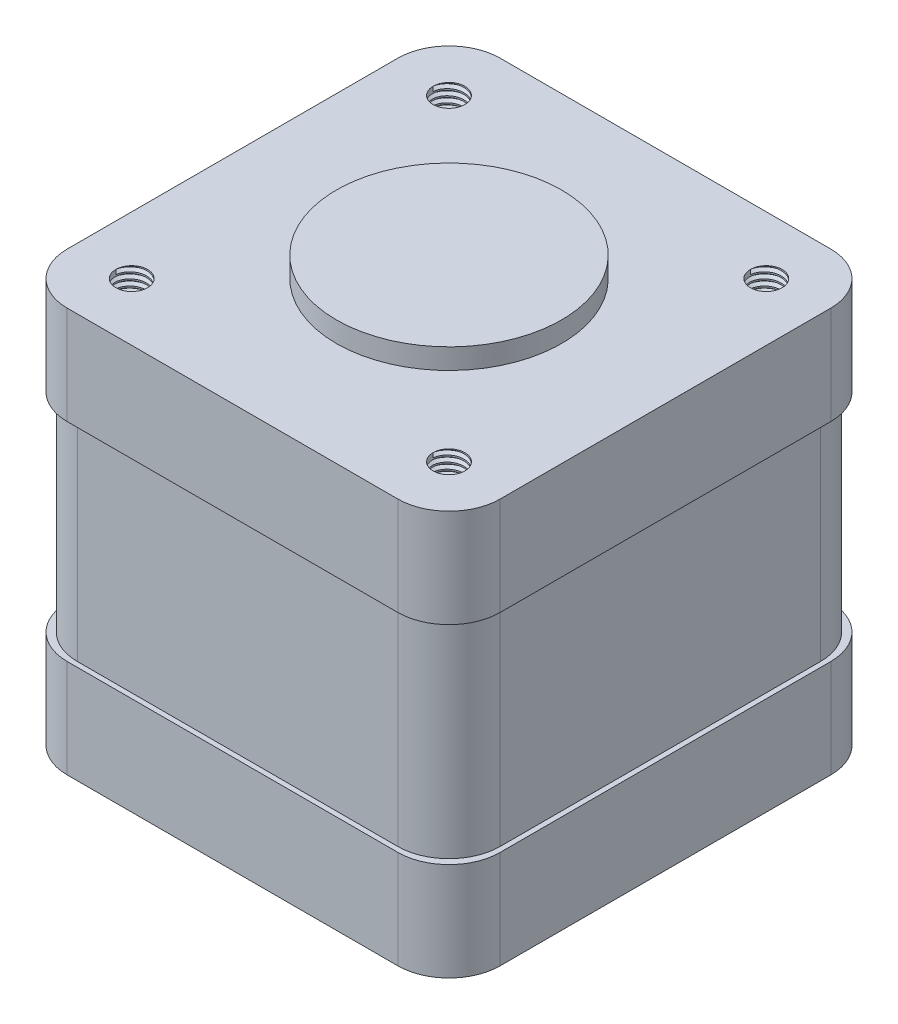
SolidWorks part; units mm, degrees
ref_plane "Front Plane" through (0, 0, 0) normal (0, 0, 1) x (1, 0, 0)
ref_plane "Top Plane" through (0, 0, 0) normal (0, 1, 0) x (1, 0, 0)
ref_plane "Right Plane" through (0, 0, 0) normal (1, 0, 0) x (0, 0, -1)
sketch "Sketch1" plane through (0, 0, 0) normal (0, 1, 0) x (1, 0, 0)
  line L1 (5, 0) -> (37.3, 0)
  line L2 (0, 5) -> (0, 37.3)
  line L3 (5, 42.3) -> (37.3, 42.3)
  line L4 (42.3, 5) -> (42.3, 37.3)
  arc A0 (5, 0) -> (0, 5) centre (5, 5) cw
  arc A1 (37.3, 0) -> (42.3, 5) centre (37.3, 5) ccw
  arc A2 (37.3, 42.3) -> (42.3, 37.3) centre (37.3, 37.3) cw
  arc A3 (0, 37.3) -> (5, 42.3) centre (5, 37.3) cw
  point P7 (0, 0)
  point P12 (42.3, 42.3)
  point P15 (0, 42.3)
  dimension "D3" = 5
  dimension "D1" = 42.3
  dimension "D2" = 42.3
extrude "Boss-Extrude1" add sketch "Sketch1" along normal blind 9.6
sketch "Sketch2" plane through (0, 9.6, 0) normal (0, 1, 0) x (1, 0, 0)
  line L0 (0, 37.3) -> (0, 5) construction
  line L1 (5.5, 0.4967) -> (36.8, 0.4967)
  line L2 (0.5, 5.4967) -> (0.5, 36.8)
  line L3 (5.5, 41.8) -> (36.8, 41.8)
  line L4 (41.8, 5.4967) -> (41.8, 36.8)
  line L5 (37.3, 42.3) -> (5, 42.3) construction
  line L6 (42.3, 5) -> (42.3, 37.3) construction
  line L7 (5, 0) -> (37.3, 0) construction
  arc A0 (5.5, 0.4967) -> (0.5, 5.4967) centre (5.5, 5.4967) cw
  arc A1 (36.8, 0.4967) -> (41.8, 5.4967) centre (36.8, 5.4967) ccw
  arc A2 (36.8, 41.8) -> (41.8, 36.8) centre (36.8, 36.8) cw
  arc A3 (0.5, 36.8) -> (5.5, 41.8) centre (5.5, 36.8) cw
  dimension "D5" = 5
  dimension "D1" = 0.5
  dimension "D2" = 0.5
  dimension "D3" = 0.5
  dimension "D4" = 0.4967
extrude "Boss-Extrude2" add sketch "Sketch2" along normal blind 20.3
sketch "Sketch3" plane through (0, 29.9, 0) normal (0, 1, 0) x (1, 0, 0)
  line L0 (0, 37.3) -> (0, 5) construction
  line L1 (5, 42.3) -> (37.3, 42.3)
  line L2 (0, 37.3) -> (0, 5)
  line L3 (5, 0) -> (37.3, 0)
  line L4 (42.3, 37.3) -> (42.3, 5)
  line L5 (37.3, 42.3) -> (5, 42.3) construction
  line L7 (5.5, 0.4967) -> (36.8, 0.4967) construction
  line L8 (41.8, 5.4967) -> (41.8, 36.8) construction
  arc A0 (37.3, 42.3) -> (42.3, 37.3) centre (37.3, 37.3) cw
  arc A1 (37.3, 0) -> (42.3, 5) centre (37.3, 5) ccw
  arc A2 (0, 5) -> (5, 0) centre (5, 5) ccw
  arc A3 (5, 42.3) -> (0, 37.3) centre (5, 37.3) ccw
  point P10 (42.3, 42.3)
  point P15 (0, 0)
  point P18 (0, 42.3)
  dimension "D3" = 5
  dimension "D4" = 0.4967
  dimension "D1" = 42.3
  dimension "D2" = 42.3
  dimension "D5" = 0.5
extrude "Boss-Extrude3" add sketch "Sketch3" along normal blind 9.6
sketch "Sketch4" plane through (0, 39.5, 0) normal (0, 1, 0) x (1, 0, 0)
  line L0 (21.15, 42.3) -> (21.15, 0) construction
  line L1 (37.3, 42.3) -> (5, 42.3) construction
  line L2 (5, 0) -> (37.3, 0) construction
  line L3 (0, 21.15) -> (42.3, 21.15) construction
  line L4 (0, 37.3) -> (0, 5) construction
  line L5 (42.3, 5) -> (42.3, 37.3) construction
  circle A0 centre (5.65, 36.65) radius 1.55
  circle A1 centre (36.65, 36.65) radius 1.55
  circle A2 centre (5.65, 5.65) radius 1.55
  circle A3 centre (36.65, 5.65) radius 1.55
  point P14 (21.15, 21.15)
  dimension "D2" = 15.5
  dimension "D3" = 3.1
  dimension "D1" = 15.5
extrude "Cut-Extrude1" cut sketch "Sketch4" against normal blind 4.5
thread "MinColWidth_OnTracking2" pitch 0.6 start angle 0, offset 0, length 4.5, pitch 0.6, diameter 3.1
ref_plane "Plane2" through (4.1, 39.5, -36.65) normal (0, 0, 1) x (-1, 0, 0)
sketch "HeaderRowsCount2" plane through (4.1, 39.5, -36.65) normal (0, 0, 1) x (-1, 0, 0)
  line L0 (0, 0) -> (0, 0.6) construction
  line L1 (0, 0) -> (0.3248, 0.1875)
  line L2 (0.3248, 0.1875) -> (0.3248, 0.2625)
  line L3 (0.3248, 0.2625) -> (0, 0.45)
  line L4 (0.3248, 0.225) -> (0, 0.225) construction
  line L11 (0, 0) -> (0, 0.45)
  point P2 (0, 0)
  dimension "Pitch" = 0.6
  dimension "Profile_Angle" = 60
  dimension "Profile_Land" = 0.075
  dimension "Profile_Height" = 0.3248
thread "MinColWidth_OnTracking3" pitch 0.6 profile "HeaderRowsCount3" start angle 0, offset 0, length 4.5, pitch 0.6, diameter 3.1
ref_plane "Plane3" through (35.1, 39.5, -36.65) normal (0, 0, 1) x (-1, 0, 0)
sketch "HeaderRowsCount3" plane through (35.1, 39.5, -36.65) normal (0, 0, 1) x (-1, 0, 0)
  line L0 (0, 0) -> (0, 0.6) construction
  line L1 (0, 0) -> (0.3248, 0.1875)
  line L2 (0.3248, 0.1875) -> (0.3248, 0.2625)
  line L3 (0.3248, 0.2625) -> (0, 0.45)
  line L4 (0.3248, 0.225) -> (0, 0.225) construction
  line L11 (0, 0) -> (0, 0.45)
  point P2 (0, 0)
  dimension "Pitch" = 0.6
  dimension "Profile_Angle" = 60
  dimension "Profile_Land" = 0.075
  dimension "Profile_Height" = 0.3248
thread "MinColWidth_OnTracking4" pitch 0.6 profile "HeaderRowsCount4" start angle 0, offset 0, length 4.5, pitch 0.6, diameter 3.1
ref_plane "Plane4" through (4.1, 39.5, -5.65) normal (0, 0, 1) x (-1, 0, 0)
sketch "HeaderRowsCount4" plane through (4.1, 39.5, -5.65) normal (0, 0, 1) x (-1, 0, 0)
  line L0 (0, 0) -> (0, 0.6) construction
  line L1 (0, 0) -> (0.3248, 0.1875)
  line L2 (0.3248, 0.1875) -> (0.3248, 0.2625)
  line L3 (0.3248, 0.2625) -> (0, 0.45)
  line L4 (0.3248, 0.225) -> (0, 0.225) construction
  line L11 (0, 0) -> (0, 0.45)
  point P2 (0, 0)
  dimension "Pitch" = 0.6
  dimension "Profile_Angle" = 60
  dimension "Profile_Land" = 0.075
  dimension "Profile_Height" = 0.3248
thread "MinColWidth_OnTracking5" pitch 0.6 profile "HeaderRowsCount5" start angle 0, offset 0, length 4.5, pitch 0.6, diameter 3.1
ref_plane "Plane5" through (35.1, 39.5, -5.65) normal (0, 0, 1) x (-1, 0, 0)
sketch "HeaderRowsCount5" plane through (35.1, 39.5, -5.65) normal (0, 0, 1) x (-1, 0, 0)
  line L0 (0, 0) -> (0, 0.6) construction
  line L1 (0, 0) -> (0.3248, 0.1875)
  line L2 (0.3248, 0.1875) -> (0.3248, 0.2625)
  line L3 (0.3248, 0.2625) -> (0, 0.45)
  line L4 (0.3248, 0.225) -> (0, 0.225) construction
  line L11 (0, 0) -> (0, 0.45)
  point P2 (0, 0)
  dimension "Pitch" = 0.6
  dimension "Profile_Angle" = 60
  dimension "Profile_Land" = 0.075
  dimension "Profile_Height" = 0.3248
sketch "Sketch18" plane through (0, 39.5, 0) normal (0, 1, 0) x (1, 0, 0)
  line L0 (0, 21.15) -> (42.3, 21.15) construction
  line L1 (0, 37.3) -> (0, 5) construction
  line L2 (42.3, 5) -> (42.3, 37.3) construction
  line L3 (21.15, 42.3) -> (21.15, 0) construction
  line L4 (37.3, 42.3) -> (5, 42.3) construction
  line L5 (5, 0) -> (37.3, 0) construction
  circle A0 centre (21.15, 21.15) radius 11
  dimension "D1" = 22
extrude "Boss-Extrude4" add sketch "Sketch18" along normal blind 2
